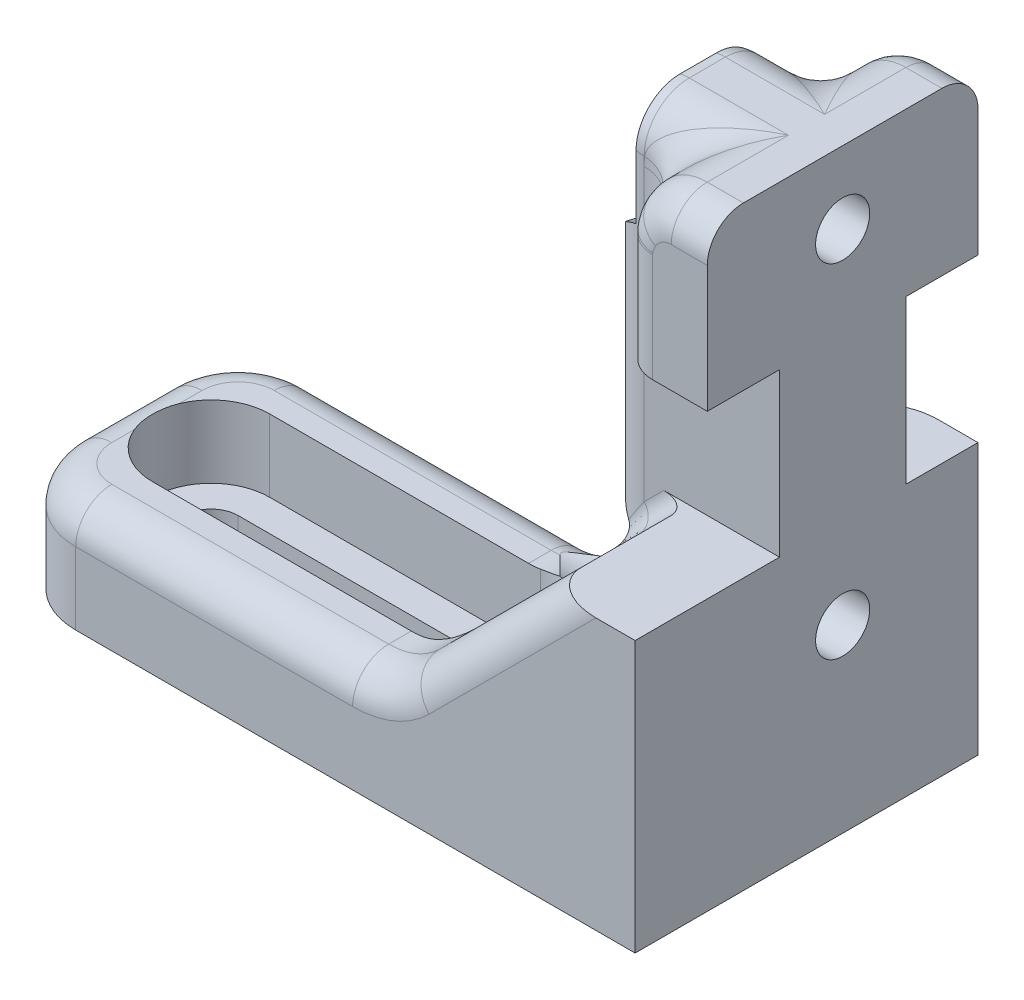
SolidWorks part; units mm, degrees
material "ABS"
ref_plane "Спереди" through (0, 0, 0) normal (0, 0, 1) x (1, 0, 0)
ref_plane "Сверху" through (0, 0, 0) normal (0, 1, 0) x (1, 0, 0)
ref_plane "Справа" through (0, 0, 0) normal (1, 0, 0) x (0, 0, -1)
sketch "Эскиз1" plane through (0, 0, 0) normal (0, 1, 0) x (1, 0, 0)
  line L1 (0, 0) -> (30, 0)
  line L2 (0, 0) -> (0, 15)
  line L3 (0, 15) -> (30, 15)
  line L4 (30, 0) -> (30, 15)
  dimension "D1" = 15
  dimension "D2" = 30
extrude "Бобышка-Вытянуть1" add sketch "Эскиз1" along normal blind 6
sketch "Эскиз2" plane through (0, 6, 0) normal (0, 1, 0) x (1, 0, 0)
  line L0 (5, 2.5) -> (20, 2.5) construction
  line L1 (5, 4) -> (20, 4)
  line L2 (5, 1) -> (20, 1)
  line L3 (5, 2.5) -> (5, 15) construction
  line L4 (30, 15) -> (0, 15) construction
  line L6 (0, 0) -> (30, 0) construction
  line L9 (20, 2.5) -> (30, 2.5) construction
  arc A0 (5, 4) -> (5, 1) centre (5, 2.5) ccw
  arc A1 (20, 1) -> (20, 4) centre (20, 2.5) ccw
  point P2 (12.5, 2.5)
  dimension "D1" = 15
  dimension "D2" = 3
  dimension "D3" = 10
  dimension "D4" = 2.5
extrude "Вырез-Вытянуть1" cut sketch "Эскиз2" against normal through all
sketch "Эскиз3" plane through (30, 0, 0) normal (1, 0, 0) x (0, 0, -1)
  line L1 (0, 0) -> (15, 0)
  line L2 (0, 0) -> (0, 33)
  line L3 (0, 33) -> (15, 33)
  line L4 (15, 0) -> (15, 33)
  dimension "D1" = 33
extrude "Бобышка-Вытянуть3" add sketch "Эскиз3" along normal blind 5
sketch "Эскиз4" plane through (35, 0, 0) normal (1, 0, 0) x (0, 0, -1)
  line L0 (0, 33) -> (0, 0) construction
  line L1 (0, 24) -> (4, 24)
  line L2 (0, 24) -> (0, 15)
  line L3 (0, 15) -> (4, 15)
  line L4 (4, 24) -> (4, 15)
  line L5 (15, 0) -> (15, 33) construction
  line L6 (15, 24) -> (11, 24)
  line L7 (15, 24) -> (15, 15)
  line L8 (15, 15) -> (11, 15)
  line L9 (11, 24) -> (11, 15)
  line L10 (15, 33) -> (0, 33) construction
  line L11 (0, 0) -> (15, 0) construction
  line L12 (7.5, 33) -> (7.5, 0) construction
  circle A0 centre (7.5, 29) radius 1.5
  circle A1 centre (7.5, 10) radius 1.5
  dimension "D4" = 3
  dimension "D1" = 4
  dimension "D2" = 9
  dimension "D3" = 15
  dimension "D5" = 4
  dimension "D6" = 19
  dimension "D7" = 9
  dimension "D8" = 5
  dimension "D9" = 5
extrude "Вырез-Вытянуть2" cut sketch "Эскиз4" against normal blind 5
sketch "Эскиз5" plane through (30, 0, 0) normal (-1, 0, 0) x (0, 0, 1)
  line L0 (-15, 33) -> (0, 33) construction
  line L1 (-11, 33) -> (-4, 33)
  line L2 (-11, 33) -> (-11, 6)
  line L3 (-11, 6) -> (-4, 6)
  line L4 (-4, 33) -> (-4, 6)
  line L5 (0, 6) -> (-15, 6) construction
  line L6 (-15, 24) -> (-15, 33) construction
  line L7 (0, 33) -> (0, 24) construction
  dimension "D1" = 4
  dimension "D2" = 4
extrude "Бобышка-Вытянуть4" add sketch "Эскиз5" along normal blind 5
fillet "Скругление12" radius 3 2 edges at (30, 33, -2) (30, 33, -13)
sketch "Эскиз6" plane through (35, 0, 0) normal (1, 0, 0) x (0, 0, -1)
  circle A0 centre (7.5, 29) radius 1.5
  circle A1 centre (7.5, 10) radius 1.5
  dimension "D1" = 3
ref_plane "Плоскость1" through (0, 10, 0) normal (0, -1, 0) x (-1, 0, 0)
sketch "Эскиз11" plane through (0, 0, 0) normal (0, 0, 1) x (1, 0, 0)
  line L0 (35, 15) -> (30, 15)
  line L1 (30, 15) -> (30, 6)
  line L2 (30, 6) -> (0, 6)
  line L3 (0, 6) -> (0, 0)
  line L4 (0, 0) -> (35, 0)
  line L5 (35, 0) -> (35, 15)
extrude "Бобышка-Вытянуть5" add sketch "Эскиз11" along normal blind 4
sketch "Эскиз9" plane through (0, 10, 0) normal (0, -1, 0) x (-1, 0, 0)
  line L0 (-5, 2.5) -> (-20, 2.5) construction
  line L1 (-5, -0.75) -> (-20, -0.75)
  line L2 (-5, 5.75) -> (-20, 5.75)
  arc A0 (-5, -0.75) -> (-5, 5.75) centre (-5, 2.5) ccw
  arc A1 (-20, 5.75) -> (-20, -0.75) centre (-20, 2.5) ccw
  point P4 (-12.5, 2.5)
  dimension "D1" = 6.5
extrude "Вырез-Вытянуть6" cut sketch "Эскиз9" along normal blind 8
chamfer "Фаска3" distance 9 angle 45 1 edges at (30, 6, 0)
sketch "Эскиз12" plane through (0, 0, 0) normal (0, -1, 0) x (1, 0, 0)
  line L0 (0, -15) -> (0, 4) construction
  line L1 (0, -9) -> (25, -9)
  line L2 (0, -9) -> (0, -15)
  line L3 (0, -15) -> (25, -15)
  line L4 (25, -9) -> (25, -15)
  line L5 (35, -15) -> (0, -15) construction
  line L6 (5, -2.5) -> (5, -9) construction
  line L7 (5, -2.5) -> (5, 4) construction
  line L8 (0, 4) -> (35, 4) construction
  dimension "D1" = 25
extrude "Вырез-Вытянуть7" cut sketch "Эскиз12" against normal through all
extrude "Вырез-Вытянуть8" cut sketch "Эскиз6" against normal through all
fillet "Скругление26" radius 4 2 edges at (21, 6, 2.2962) (21, 6, -7.2962)
sketch "Эскиз7" plane through (0, 0, 0) normal (-1, 0, 0) x (0, 0, 1)
  circle A0 centre (-7.5, 10) radius 4
  circle A1 centre (-7.5, 29) radius 4
  dimension "D1" = 8
fillet "Скругление31" radius 3 1 edges at (25, 5, -9)
fillet "Скругление36" radius 2.5 2 edges at (25, 21.5, -4) (25, 21.5, -11)
fillet "Скругление37" radius 2.5 5 edges at (30.25, 33, -4) (25.7322, 33, -4.7322) (25, 33, -7.5) (25.7322, 33, -10.2678) (30.25, 33, -11)
fillet "Скругление38" radius 2.5 6 edges at (30.6141, 31.8186, -4.376) (30.0105, 30.2509, -4) (30.6141, 31.8186, -10.624) (30.0105, 30.2509, -11) (30, 27, -4) (30, 27, -11)
fillet "Скругление40" radius 4 2 edges at (0, 3, 4) (0, 3, -9)
fillet "Скругление41" radius 2 1 edges at (25, 5, -15)
fillet "Скругление42" radius 2 13 edges at (26.0858, 11.0858, 4) (20.8739, 6.3045, 4) (28.5, 13.5, -15) (25.5858, 10.5858, -14.4142) (25, 10, -12.5) (24.1811, 9.1811, -9.9402) (20.7643, 6.261, -9) (11.6716, 6, -9) (1.1716, 6, -7.8284) (0, 6, -2.5) (1.1716, 6, 2.8284) (11.6716, 6, 4)
extrude "Вырез-Вытянуть9" cut sketch "Эскиз7" against normal blind 27
sketch "Эскиз13" plane through (27, 0, 0) normal (-1, 0, 0) x (0, 0, 1)
  line L1 (-11.975, 29.4891) -> (-2.7677, 29.4891)
  line L2 (-11.975, 29.4891) -> (-11.975, 36.094)
  line L3 (-11.975, 36.094) -> (-2.7677, 36.094)
  line L4 (-2.7677, 29.4891) -> (-2.7677, 36.094)
  point P4 (-11.975, 29.4891)
extrude "Вырез-Вытянуть10" cut sketch "Эскиз13" along normal blind 27
fillet "Скругление43" radius 2 6 edges at (34, 33, 0) (30.8787, 32.1213, 0) (34, 33, -15) (30.8787, 32.1213, -15) (30, 27, 0) (30, 27, -15)
fillet "Скругление44" radius 1 4 edges at (27.2487, 12.2487, -10.9873) (27.2487, 12.2487, -4.0127) (28.75, 13.75, -11) (28.75, 13.75, -4)
